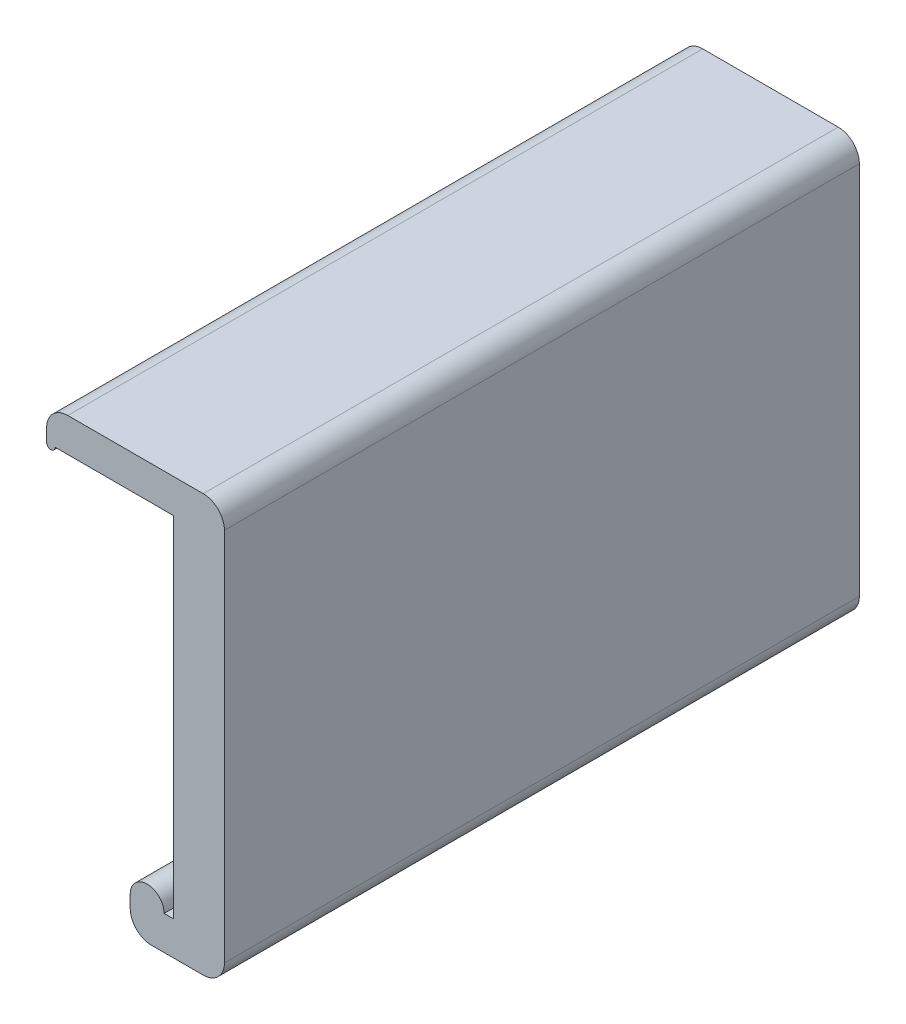
SolidWorks part; units mm, degrees
ref_plane "Front Plane" through (0, 0, 0) normal (0, 0, 1) x (1, 0, 0)
ref_plane "Top Plane" through (0, 0, 0) normal (0, 1, 0) x (1, 0, 0)
ref_plane "Right Plane" through (0, 0, 0) normal (1, 0, 0) x (0, 0, -1)
sketch "Sketch2" plane through (0, 0, 0) normal (0, 0, 1) x (1, 0, 0)
  line L0 (37.3413, 7.25) -> (37.3413, 6.45)
  line L2 (41.5413, -2.6) -> (39.3163, -2.6)
  line L4 (39.3163, -2.6) -> (39.3163, -1.8)
  line L5 (40.3413, -1.8) -> (39.3163, -1.8)
  line L13 (41.5413, -2.6) -> (41.5413, 7.25)
  line L14 (41.5413, 7.25) -> (37.3413, 7.25)
  line L17 (37.3413, 6.45) -> (40.3413, 6.45)
  line L20 (40.3413, 6.45) -> (40.3413, -1.8)
  arc A0 (39.3163, -1.8) -> (40.1163, -1.8) centre (39.7163, -1.8) cw
  arc A1 (37.3413, 6.45) -> (37.5413, 6.45) centre (37.4413, 6.45) ccw
  dimension "D3" = 0.1
  dimension "D4" = 0.4
  dimension "D1" = 3
  dimension "D2" = 0.8
  dimension "D5" = 1.2
  dimension "D6" = 9.85
  dimension "D7" = 2.225
extrude "Boss-Extrude1" add sketch "Sketch2" along normal blind 7.5 and the other way blind 7.5 contours L17 L20 L5 L4 L2 L13 L14 L0 | L17 A1 | A0 L5 region at (40.5456, 2.8004, 0) region at (37.4413, 6.4076, 0) region at (39.7163, -1.6302, 0)
fillet "Fillet1" radius 0.5 4 edges at (37.3413, 7.25, 0) (39.3163, -2.6, 0) (41.5413, -2.6, 0) (41.5413, 7.25, 0)
